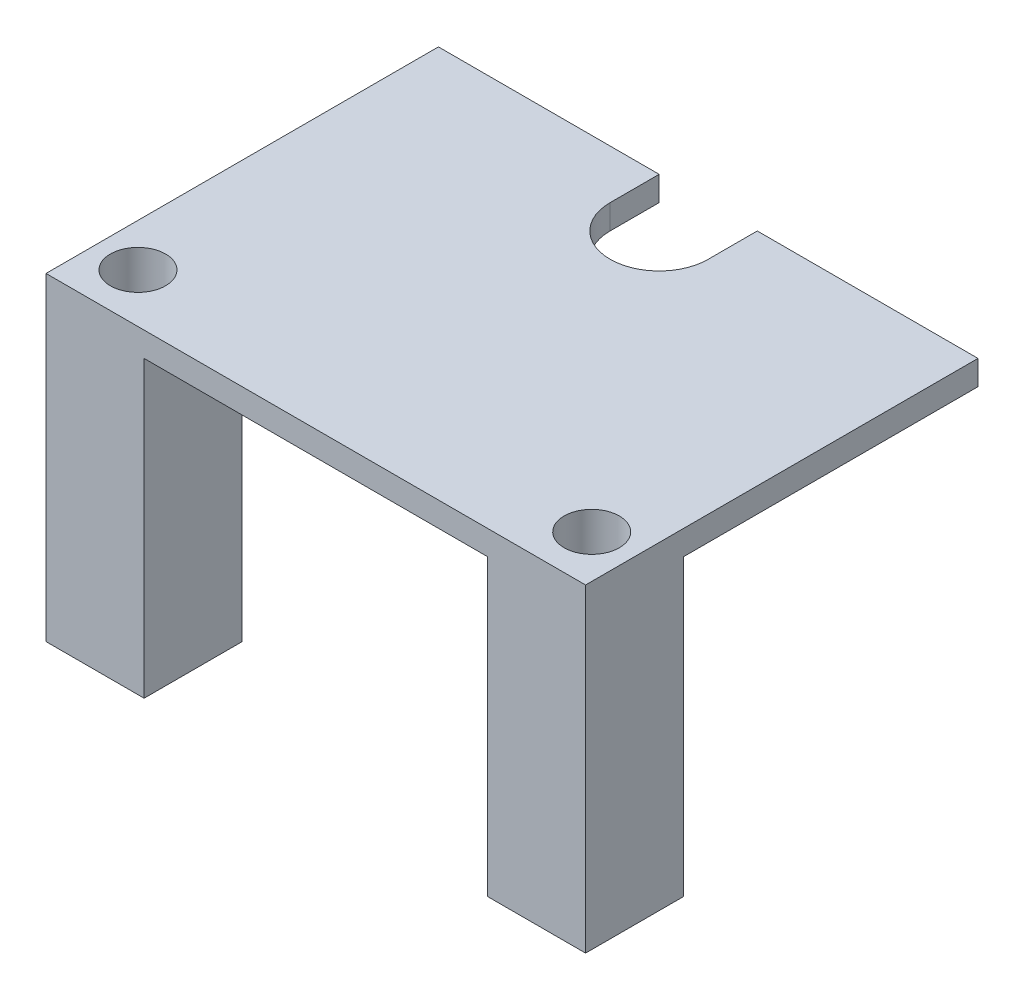
SolidWorks part; units mm, degrees
ref_plane "Front Plane" through (0, 0, 0) normal (0, 0, 1) x (1, 0, 0)
ref_plane "Top Plane" through (0, 0, 0) normal (0, 1, 0) x (1, 0, 0)
ref_plane "Right Plane" through (0, 0, 0) normal (1, 0, 0) x (0, 0, -1)
sketch "Sketch1" plane through (0, 0, 0) normal (1, 0, 0) x (0, 0, -1)
  line L0 (-12.7, 0) -> (12.7, 0)
  line L1 (12.7, 0) -> (12.7, 76.2)
  line L2 (12.7, 76.2) -> (88.9, 76.2)
  line L3 (88.9, 76.2) -> (88.9, 82.55)
  line L4 (88.9, 82.55) -> (-12.7, 82.55)
  line L5 (-12.7, 82.55) -> (-12.7, 0)
  point P4 (0, 0)
  dimension "D1" = 25.4
  dimension "D2" = 6.35
  dimension "D3" = 76.2
  dimension "D4" = 101.6
extrude "Boss-Extrude1" add sketch "Sketch1" along normal mid plane 139.7
sketch "Sketch2" plane through (0, 0, -88.9) normal (0, 0, -1) x (-1, 0, 0)
  line L0 (-44.45, 0) -> (44.45, 0)
  line L1 (44.45, 0) -> (44.45, 76.2)
  line L2 (-69.85, 76.2) -> (69.85, 76.2) construction
  line L3 (44.45, 76.2) -> (-44.45, 76.2)
  line L4 (-44.45, 76.2) -> (-44.45, 0)
  line L5 (-69.85, 0) -> (-69.85, 76.2) construction
  point P4 (0, 0)
  dimension "D1" = 25.4
extrude "Cut-Extrude1" cut sketch "Sketch2" against normal through all
hole_wizard "CBORE for 1/4 Binding Head Machine Screw1" positions "Sketch3" profile "Sketch5" counterbore size "1/4" standard "ANSI Inch" end condition through all
sketch "Sketch3" plane through (0, 82.55, 0) normal (0, 1, 0) x (1, 0, 0)
  line L0 (58.7375, 0) -> (0, 0) construction
  line L1 (0, 0) -> (-58.7375, 0) construction
  point P0 (58.7375, 0)
  point P2 (-58.7375, 0)
  dimension "D1" = 117.475
sketch "Sketch5" plane through (58.7375, 82.55, 0) normal (1, 0, 0) x (0, 0, 1)
  line L0 (0, 0) -> (0, 82.55)
  line L1 (0, 82.55) -> (3.3782, 82.55)
  line L3 (3.3782, 82.55) -> (3.3782, 64.191)
  line L4 (3.3782, 64.191) -> (7.1437, 64.191)
  line L5 (7.1437, 64.191) -> (7.1437, 0)
  line L7 (7.1437, 0) -> (0, 0)
  line L11 (0, -6.35) -> (0, 107.95) construction
  dimension "Thru Hole Dia." = 6.7564
  dimension "Thru Hole Depth" = 82.55
  dimension "C'Bore Dia." = 14.2875
  dimension "C'Bore Depth" = 64.191
sketch "Sketch6" plane through (0, 82.55, 0) normal (0, 1, 0) x (1, 0, 0)
  line L0 (0, 76.2) -> (0, 0) construction
  line L1 (69.85, -12.7) -> (-69.85, -12.7) construction
  line L2 (12.7, 76.2) -> (12.7, 88.9)
  line L3 (69.85, 88.9) -> (-69.85, 88.9) construction
  line L4 (12.7, 88.9) -> (-12.7, 88.9)
  line L5 (-12.7, 76.2) -> (-12.7, 88.9)
  arc A1 (12.7, 76.2) -> (-12.7, 76.2) centre (0, 76.2) cw
  dimension "D1" = 25.4
  dimension "D2" = 88.9
extrude "Cut-Extrude2" cut sketch "Sketch6" against normal through all
